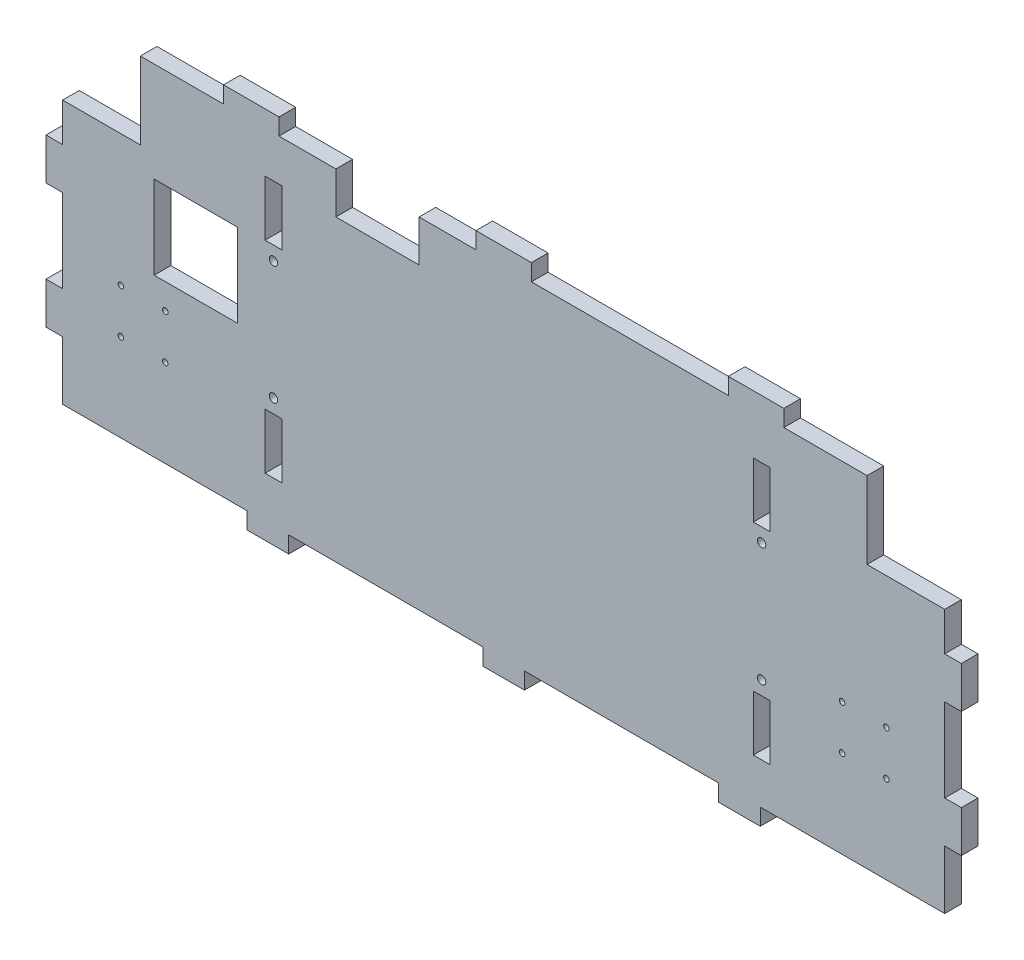
SolidWorks part; units mm, degrees
ref_plane "Plan de face" through (0, 0, 0) normal (0, 0, 1) x (1, 0, 0)
ref_plane "Plan de dessus" through (0, 0, 0) normal (0, 1, 0) x (1, 0, 0)
ref_plane "Plan de droite" through (0, 0, 0) normal (1, 0, 0) x (0, 0, -1)
sketch "Esquisse1" plane through (0, 0, 0) normal (0, 0, 1) x (1, 0, 0)
  line L0 (-159, 35) -> (-131, 35)
  line L1 (0, 102.0551) -> (0, -193.4247) construction
  line L2 (-159, 35) -> (-159, -60)
  line L3 (-159, -60) -> (159, -60)
  line L4 (159, 35) -> (159, -60)
  line L6 (131, 35) -> (131, 62.75)
  line L7 (131, 62.75) -> (-131, 62.75)
  line L8 (-131, 35) -> (-131, 62.75)
  line L9 (159, 35) -> (131, 35)
  line L10 (96, 47.75) -> (90, 47.75)
  line L11 (96, 47.75) -> (96, 27.75)
  line L12 (96, 27.75) -> (90, 27.75)
  line L13 (90, 47.75) -> (90, 27.75)
  line L14 (96, -25.01) -> (90, -25.01)
  line L15 (96, -25.01) -> (96, -45.01)
  line L16 (96, -45.01) -> (90, -45.01)
  line L17 (90, -25.01) -> (90, -45.01)
  line L18 (-80, 47.75) -> (-86, 47.75)
  line L19 (-80, 47.75) -> (-80, 27.75)
  line L20 (-80, 27.75) -> (-86, 27.75)
  line L21 (-86, 47.75) -> (-86, 27.75)
  line L22 (-80, -25.01) -> (-86, -25.01)
  line L23 (-80, -25.01) -> (-80, -45.01)
  line L24 (-80, -45.01) -> (-86, -45.01)
  line L25 (-86, -25.01) -> (-86, -45.01)
  line L26 (-95.9865, 26.8256) -> (-125.9865, 26.8256)
  line L27 (-95.9865, 26.8256) -> (-95.9865, -3.1744)
  line L28 (-95.9865, -3.1744) -> (-125.9865, -3.1744)
  line L29 (-125.9865, 26.8256) -> (-125.9865, -3.1744)
  dimension "D1" = 95
  dimension "D2" = 28
  dimension "D3" = 28
  dimension "D4" = 95
  dimension "D6" = 262
  dimension "D7" = 122.75
  dimension "D5" = 159
  dimension "D8" = 318
  dimension "D9" = 6
  dimension "D10" = 20
  dimension "D11" = 20
  dimension "D12" = 6
  dimension "D13" = 6
  dimension "D14" = 20
  dimension "D15" = 6
  dimension "D16" = 20
  dimension "D17" = 52.76
  dimension "D18" = 63
  dimension "D19" = 73
  dimension "D20" = 73
  dimension "D21" = 52.76
  dimension "D22" = 15
  dimension "D23" = 15
  dimension "D24" = 63
  dimension "D25" = 30
  dimension "D26" = 30
extrude "Boss.-Extru.1" add sketch "Esquisse1" along normal blind 6
sketch "Esquisse2" plane through (0, 0, 6) normal (0, 0, 1) x (1, 0, 0)
  line L0 (-159, -60) -> (159, -60) construction
  line L1 (-92.5, -60) -> (-77.5, -60)
  line L2 (-92.5, -60) -> (-92.5, -66)
  line L3 (-92.5, -66) -> (-77.5, -66)
  line L4 (-77.5, -60) -> (-77.5, -66)
  line L5 (-159, 35) -> (-159, -60) construction
  line L6 (-7.5, -60) -> (7.5, -60)
  line L7 (-7.5, -60) -> (-7.5, -66)
  line L8 (-7.5, -66) -> (7.5, -66)
  line L9 (7.5, -60) -> (7.5, -66)
  line L10 (77.5, -60) -> (92.5, -60)
  line L11 (77.5, -60) -> (77.5, -66)
  line L12 (77.5, -66) -> (92.5, -66)
  line L13 (92.5, -60) -> (92.5, -66)
  line L14 (176.2958, 0) -> (-249.7093, -3.2925) construction
  line L15 (0, 107.6082) -> (0, -117.4775) construction
  line L16 (-131, 35) -> (-159, 35) construction
  line L17 (-159, 21.09) -> (-165, 21.09)
  line L18 (-159, 21.09) -> (-159, 6.09)
  line L19 (-159, 6.09) -> (-165, 6.09)
  line L20 (-165, 21.09) -> (-165, 6.09)
  line L21 (-159, -23.91) -> (-165, -23.91)
  line L22 (-159, -23.91) -> (-159, -38.91)
  line L23 (-159, -38.91) -> (-165, -38.91)
  line L24 (-165, -23.91) -> (-165, -38.91)
  line L25 (165, -23.91) -> (165, -38.91)
  line L26 (159, -38.91) -> (165, -38.91)
  line L27 (159, -23.91) -> (159, -38.91)
  line L28 (159, -23.91) -> (165, -23.91)
  line L29 (165, 21.09) -> (165, 6.09)
  line L30 (159, 6.09) -> (165, 6.09)
  line L31 (159, 21.09) -> (159, 6.09)
  line L32 (159, 21.09) -> (165, 21.09)
  line L33 (131, 62.75) -> (-131, 62.75) construction
  line L34 (101, 62.75) -> (81, 62.75)
  line L35 (101, 62.75) -> (101, 68.75)
  line L36 (101, 68.75) -> (81, 68.75)
  line L37 (81, 62.75) -> (81, 68.75)
  line L38 (-131, 62.75) -> (-131, 35) construction
  line L39 (-81, 62.75) -> (-101, 62.75)
  line L40 (-81, 62.75) -> (-81, 68.75)
  line L41 (-81, 68.75) -> (-101, 68.75)
  line L42 (-101, 62.75) -> (-101, 68.75)
  line L43 (10, 62.75) -> (-10, 62.75)
  line L44 (10, 62.75) -> (10, 68.75)
  line L45 (10, 68.75) -> (-10, 68.75)
  line L46 (-10, 62.75) -> (-10, 68.75)
  line L47 (131, 35) -> (131, 62.75) construction
  dimension "D1" = 66.5
  dimension "D2" = 70
  dimension "D3" = 15
  dimension "D4" = 15
  dimension "D5" = 70
  dimension "D6" = 15
  dimension "D7" = 6
  dimension "D8" = 6
  dimension "D9" = 6
  dimension "D10" = 6
  dimension "D11" = 13.91
  dimension "D12" = 15
  dimension "D13" = 30
  dimension "D14" = 15
  dimension "D15" = 20
  dimension "D16" = 20
  dimension "D17" = 20
  dimension "D18" = 30
  dimension "D19" = 30
  dimension "D20" = 121
  dimension "D21" = 6
  dimension "D22" = 6
  dimension "D23" = 6
  dimension "D24" = 6
extrude "Boss.-Extru.2" add sketch "Esquisse2" against normal blind 6
sketch "Esquisse3" plane through (0, 0, 0) normal (0, 0, -1) x (-1, 0, 0)
  line L0 (159, -60) -> (92.5, -60) construction
  line L1 (159, 6.09) -> (159, -23.91) construction
  line L2 (0, 141.59) -> (0, -167.3887) construction
  line L3 (83, 57.185) -> (83, -52.5738) construction
  line L4 (-93, 52.3657) -> (-93, -53.0892) construction
  line L5 (-90, 27.75) -> (-96, 27.75) construction
  line L6 (-96, 27.75) -> (-96, 47.75) construction
  line L7 (-96, -25.01) -> (-90, -25.01) construction
  line L8 (80, -25.01) -> (86, -25.01) construction
  line L9 (80, -45.01) -> (80, -25.01) construction
  line L10 (86, 27.75) -> (80, 27.75) construction
  circle A0 centre (138, -28.38) radius 1
  circle A1 centre (138, -12.38) radius 1
  circle A2 centre (122, -12.38) radius 1
  circle A3 centre (122, -28.38) radius 1
  circle A4 centre (-122, -28.38) radius 1
  circle A5 centre (-122, -12.38) radius 1
  circle A6 centre (-138, -12.38) radius 1
  circle A7 centre (-138, -28.38) radius 1
  circle A9 centre (83, 22.75) radius 1.5
  circle A10 centre (83, -20.01) radius 1.5
  circle A13 centre (-93, 22.75) radius 1.5
  circle A14 centre (-93, -20.01) radius 1.5
  dimension "D1" = 31.62
  dimension "D2" = 21
  dimension "D7" = 2
  dimension "D8" = 2
  dimension "D9" = 2
  dimension "D10" = 2
  dimension "D11" = 3
  dimension "D12" = 3
  dimension "D13" = 3
  dimension "D14" = 3
  dimension "D17" = 5
  dimension "D18" = 5
  dimension "D20" = 5
  dimension "D3" = 16
  dimension "D4" = 16
  dimension "D5" = 16
  dimension "D6" = 16
  dimension "D15" = 5
  dimension "D16" = 3
  dimension "D19" = 3
extrude "Enlèv. mat.-Extru.1" cut sketch "Esquisse3" against normal blind 6
sketch "Esquisse4" plane through (0, 0, 0) normal (0, 0, -1) x (-1, 0, 0)
  line L0 (10, 62.75) -> (81, 62.75) construction
  line L1 (30.5, 62.75) -> (60.5, 62.75)
  line L2 (30.5, 62.75) -> (30.5, 47.75)
  line L3 (30.5, 47.75) -> (60.5, 47.75)
  line L4 (60.5, 62.75) -> (60.5, 47.75)
  line L5 (10, 68.75) -> (10, 62.75) construction
  dimension "D1" = 20.5
  dimension "D2" = 30
  dimension "D3" = 15
extrude "Enlèv. mat.-Extru.2" cut sketch "Esquisse4" against normal blind 6
equation "\"D5@Esquisse1\"=\"D8@Esquisse1\"/2"
